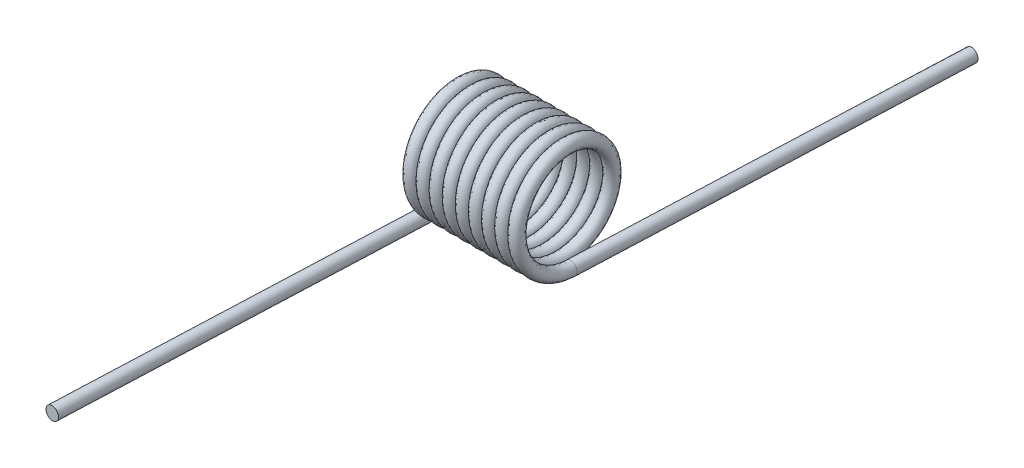
SolidWorks part; units mm, degrees
ref_plane "Front" through (0, 0, 0) normal (0, 0, 1) x (1, 0, 0)
ref_plane "Top" through (0, 0, 0) normal (0, 1, 0) x (1, 0, 0)
ref_plane "Right" through (0, 0, 0) normal (1, 0, 0) x (0, 0, -1)
sketch "Sketch1" plane through (0, 0, 0) normal (1, 0, 0) x (0, 0, -1)
  line L0 (0, -11.6713) -> (0, -15.1003) construction
  line L1 (0, -15.1003) -> (101.6, -15.1003) construction
  line L2 (0, -15.1003) -> (-101.6, -15.1003) construction
  line L3 (0, 0) -> (15.1003, 0) construction
  line L4 (0, 0) -> (0, -15.1003) construction
  line L5 (-101.6, -15.1003) -> (-101.6, -11.6713) construction
  line L6 (-101.6, -11.6713) -> (0, -11.6713) construction
  line L7 (101.6, -15.1003) -> (101.6, -11.6713) construction
  line L8 (101.6, -11.6713) -> (0, -11.6713) construction
  circle A0 centre (0, 0) radius 15.1003 construction
  circle A1 centre (0, 0) radius 9.3345 construction
  circle A2 centre (0, 0) radius 13.3858 construction
  point P7 (0, -13.3858)
  point P10 (0, 15.1003)
  dimension "OD" = 30.2006
  dimension "For Shaft Diameter" = 18.669
  dimension "Wire Diameter" = 3.429
  dimension "Leg Length" = 101.6
  dimension "Deflection Angle" = 180
sketch "Sketch2" plane through (0, 0, 0) normal (1, 0, 0) x (0, 0, -1)
  circle A0 centre (0, 0) radius 13.3858 construction
  circle A2 centre (0, 0) radius 13.3858
curve "Helix/Spiral1" pitch 3.4544 height 31.0896 radius 13.3858 centre (0, 0, 0) axis (1, 0, 0) start towards (0, 0, -1)
ref_plane "Plane1" through (0, -13.3858, 0) normal (0.041, 0, -0.9992) x (0.9989, -0.0232, 0.041)
sketch "Sketch3" plane through (0, -13.3858, 0) normal (0.041, 0, -0.9992) x (0.9989, -0.0232, 0.041)
  circle A0 centre (0, 0) radius 1.7145
  dimension "D1" = 3.429
sweep "Sweep1" add profiles "Sketch3" path "Helix/Spiral1"
sketch "Sketch4" plane through (0, 0, 0) normal (-0.041, 0, 0.9992) x (-0.9989, 0.0232, -0.041)
  circle A1 centre (-0.311, 13.3822) radius 1.7145
  circle A2 centre (-0.311, 13.3822) radius 1.7145
  dimension "D1" = 0
extrude "Extrude1" add sketch "Sketch4" along normal blind 101.6
sketch "Sketch5" plane through (0.0524, 0, -1.2748) normal (0.041, 0, -0.9992) x (-0.9983, -0.0411, -0.041)
  circle A1 centre (-30.4877, -14.6497) radius 1.7145
  circle A2 centre (-30.4877, -14.6497) radius 1.7145
  dimension "D1" = 0
extrude "Extrude2" add sketch "Sketch5" along normal blind 101.6
sketch "Sketch6" plane through (0, 0, 0) normal (1, 0, 0) x (0, 0, -1)
  circle A2 centre (0, 0) radius 11.6713 construction
equation "\"D4@Helix/Spiral1\" = \"Wire Diameter@Sketch1\" + .001"
equation "\"D1@Sketch3\"=\"Wire Diameter@Sketch1\""
equation "\"D1@Extrude2\"=\"Leg Length@Sketch1\""
equation "\"Leg Length@Extrude1\"=\"Leg Length@Sketch1\""
